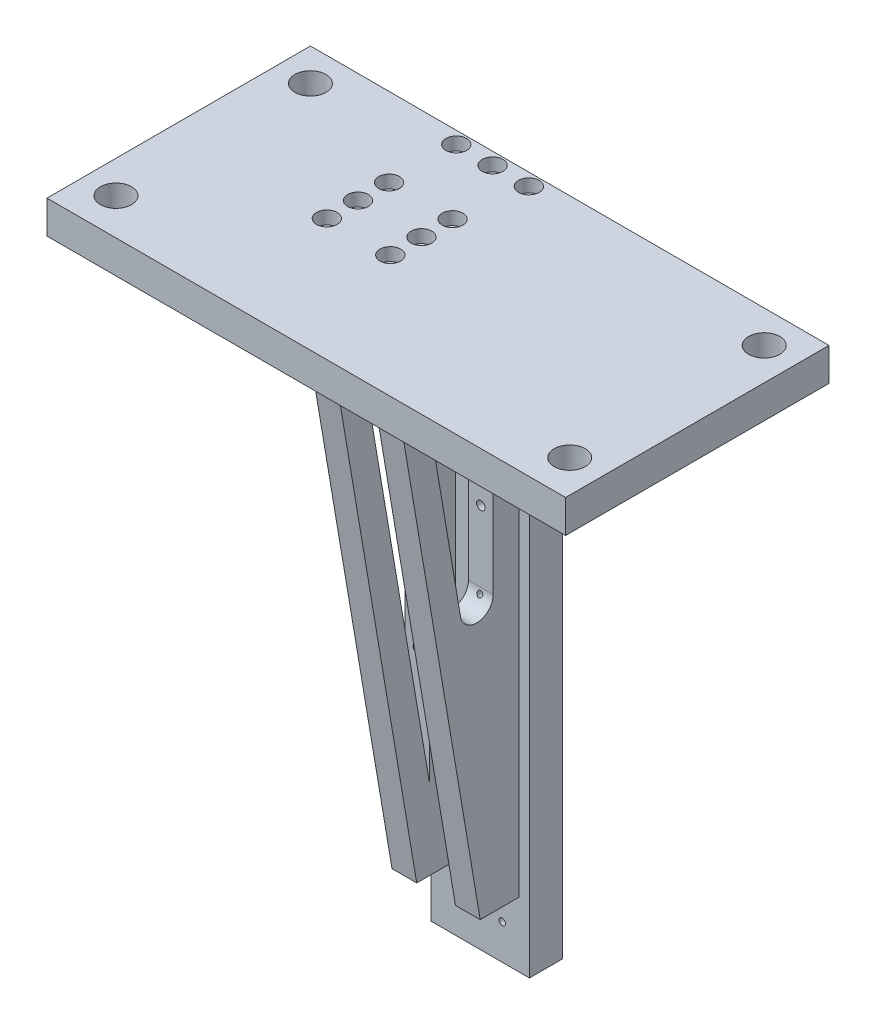
SolidWorks part; units mm, degrees
other "IGNORE"
ref_plane "Front Plane" through (0, 0, 0) normal (0, 0, 1) x (1, 0, 0)
ref_plane "Top Plane" through (0, 0, 0) normal (0, 1, 0) x (1, 0, 0)
ref_plane "Right Plane" through (0, 0, 0) normal (1, 0, 0) x (0, 0, -1)
sketch "Sketch1" plane through (0, 0, 0) normal (1, 0, 0) x (0, 0, -1)
  line L0 (-92.075, 0) -> (9.525, 0)
  line L2 (0, 0) -> (9.525, 0)
  line L4 (9.525, 9.525) -> (-92.075, 9.525)
  line L5 (-92.075, 9.525) -> (-92.075, 0)
  line L7 (0, 0) -> (9.525, 0)
  line L8 (0, 0) -> (0, -250)
  line L9 (0, -250) -> (9.525, -250)
  line L10 (9.525, 0) -> (9.525, -250)
  line L16 (9.525, 9.525) -> (9.525, 0)
  line L17 (-5.005, 0) -> (-5.005, -3.175)
  line L19 (-92.075, 0) -> (-92.075, -3.175)
  line L20 (-92.075, -3.175) -> (9.525, -3.175)
  dimension "D1" = 9.525
  dimension "D2" = 9.525
  dimension "D3" = 101.6
  dimension "D5" = 250
  dimension "D7" = 12.7
  dimension "14.53" = 14.53
extrude "Boss-Extrude5" add sketch "Sketch1" along normal blind 125 and the other way blind 75 contours L16 L4 L5 L0 | L19 L20 L17 L0 region at (0, 4.7625, 41.275) region at (0, -1.5875, 48.54)
extrude "Boss-Extrude6" add sketch "Sketch1<5>" along normal mid plane 38 separate body contours L10 L0 L8 L9 | L8 L20 L10 L0 region at (0, -1.5875, -4.7625) region at (0, -126.5875, -4.7625)
sketch "Sketch1<5>" plane through (0, 0, 0) normal (1, 0, 0) x (0, 0, -1) same geometry as "Sketch1"
sketch "Sketch2" plane through (0, 0, -9.525) normal (0, 0, -1) x (-1, 0, 0)
  line L0 (0, 0) -> (0, -263.8174) construction
  line L1 (-19, 0) -> (-15, 0)
  line L2 (-15, -4.5282) -> (15, -4.5282)
  line L3 (-15, -4.5282) -> (-15, -36.0894)
  line L4 (-15, -36.0894) -> (15, -36.0894)
  line L5 (15, -4.5282) -> (15, -36.0894)
  line L6 (-19, 0) -> (19, 0) construction
  line L7 (-15, 0) -> (-15, -250)
  line L8 (-19, -250) -> (19, -250) construction
  line L9 (-15, -250) -> (-19, -250)
  line L10 (-19, -250) -> (-19, 0)
  line M8 (19, 0) -> (-19, 0)
  line M9 (-19, 0) -> (-19, -250)
  line M10 (-19, -250) -> (19, -250)
  dimension "D1" = 30
  dimension "D2" = 4
extrude "Boss-Extrude7" add sketch "Sketch2" along normal blind 3.175 contours L7 L3 M8 M9 M10 region at (17, -125, -9.525)
sketch "Sketch6" plane through (0, 0, 0) normal (0, -1, 0) x (1, 0, 0)
  line L0 (19, 0) -> (-19, 0) construction
  line L1 (-10, 5.005) -> (10, 5.005)
  line L2 (-10, 5.005) -> (-10, 0)
  line L3 (-10, 0) -> (10, 0)
  line L4 (10, 5.005) -> (10, 0)
  line L5 (0, 0) -> (0, 18.4937) construction
  line L6 (0, -9.525) -> (0, 92.075) construction
  line L7 (19, 0) -> (19, -12.7) construction
  line L8 (19, -2.525) -> (24, -2.525)
  line L9 (19, -2.525) -> (19, -7.525)
  line L10 (19, -7.525) -> (24, -7.525)
  line L11 (24, -2.525) -> (24, -7.525)
  line L12 (-75, -9.525) -> (125, -9.525) construction
  line L13 (-75, 5.005) -> (125, 5.005) construction
  dimension "D2" = 20
  dimension "D3" = 2
  dimension "D4" = 5
  dimension "D5" = 5
extrude "Boss-Extrude8" add sketch "Sketch6" along normal up to vertex (3.175 mm away) up to point (0, -3.175, 92.075)
sketch "Sketch3" plane through (0, 0, 0) normal (0, 1, 0) x (1, 0, 0)
  line L0 (0, 0) -> (0, 9.525) construction
  line L1 (-19, 4.7625) -> (19, 4.7625) construction
  line L2 (-19, 0) -> (-19, 9.525) construction
  line L3 (19, 0) -> (19, 12.7) construction
  line L4 (0, 8.8001) -> (0, 1.2807) construction
  circle A0 centre (-14, 4.7625) radius 2
  circle A1 centre (0, 4.7625) radius 2
  circle A2 centre (14, 4.7625) radius 2
  dimension "D1" = 4
  dimension "D2" = 14
sketch "Sketch7" plane through (0, 0, -9.525) normal (0, 0, -1) x (-1, 0, 0)
  line L0 (-15, 0) -> (-15, -250) construction
  line L1 (-15, -10.1116) -> (-5.475, -10.1116)
  line L2 (-15, -10.1116) -> (-15, -28.0084)
  line L3 (-15, -28.0084) -> (-5.475, -28.0084)
  line L4 (-5.475, -10.1116) -> (-5.475, -28.0084)
  line L5 (9.475, -9.6486) -> (19, -9.6486)
  line L6 (9.475, -9.6486) -> (9.475, -28.9758)
  line L7 (9.475, -28.9758) -> (19, -28.9758)
  line L8 (19, -9.6486) -> (19, -28.9758)
  line L9 (19, 0) -> (19, -250) construction
  dimension "D1" = 9.525
sketch "Sketch5" plane through (0, 0, 0) normal (1, 0, 0) x (0, 0, -1)
  line L0 (-50.8, -3.175) -> (-50.8, -13.175)
  line L1 (-25, -3.175) -> (-25, -11.825)
  line L2 (-50.8, -13.175) -> (-15, -225)
  line L3 (-15, -225) -> (0, -225)
  line L4 (0, 0) -> (0, -250) construction
  line L5 (0, -225) -> (0, -3.175)
  line L6 (0, -3.175) -> (-50.8, -3.175)
  line L7 (0, -250) -> (9.525, -250) construction
  line L9 (-15, -3.175) -> (-15, -11.825)
  line L10 (-8.65, -18.175) -> (0, -18.175)
  line L11 (-8.65, -28.175) -> (0, -28.175)
  line L12 (-40.6582, -13.175) -> (-10, -194.5764)
  line L13 (-10, -194.5764) -> (-10, -194.5764)
  line L14 (-10, -194.5764) -> (-10, -28.1192)
  line L16 (-40.6582, -13.175) -> (-40.6582, -13.175)
  line L17 (-24.9442, -13.175) -> (-40.6582, -13.175)
  line L18 (-10, -13.175) -> (-40.6582, -13.175) construction
  line L19 (-10, -194.5764) -> (-10, -13.175) construction
  line L20 (-92.075, -3.175) -> (-5.005, -3.175) construction
  arc A0 (-15, -11.825) -> (-8.65, -18.175) centre (-8.65, -11.825) ccw
  arc A1 (-25, -11.825) -> (-8.65, -28.175) centre (-8.65, -11.825) ccw
  point P18 (-15, -18.175)
  dimension "D8" = 6.35
  dimension "D1" = 50.8
  dimension "D2" = 15
  dimension "D3" = 25
  dimension "D4" = 10
  dimension "D5" = 221.825
  dimension "D6" = 15
  dimension "D7" = 15
  dimension "D9" = 10
  dimension "D10" = 10
extrude "Boss-Extrude9" add sketch "Sketch5" along normal up to vertex (15 mm away) from vertex separate body contours L10 L9 L6 L0 L2 L3 L5 | L1 A1 L11 L5 L10 A0 L9 L6 region at (0, -5.4507, 37.9) region at (0, -17.4592, 14.2842) up to point (15, -28.0084, -9.525) starting at point (5.475, -28.0084, -9.525)
extrude "Boss-Extrude10" add sketch "Sketch5<3>" against normal up to vertex (19 mm away) from vertex separate body contours L10 L9 L6 L0 L2 L3 L5 | L1 A1 L11 L5 L10 A0 L9 L6 region at (0, -5.4507, 37.9) region at (0, -17.4592, 14.2842) up to point (-19, -9.6486, -9.525) starting at point (-9.475, -9.6486, -9.525)
sketch "Sketch5<3>" plane through (0, 0, 0) normal (1, 0, 0) x (0, 0, -1) same geometry as "Sketch5"
fillet "Fillet1" radius 6.35 4 edges at (10.2375, -194.5764, 10) (10.2375, -28.1192, 10) (10.2375, -13.175, 24.9442) (10.2375, -13.175, 40.6582)
ref_plane "Plane1" through (-2, 0, 0) normal (1, 0, 0) x (0, 0, -1)
sketch "Sketch9" plane through (0, 0, 0) normal (0, 0, -1) x (-1, 0, 0)
  line L0 (-10.2375, -18.175) -> (-10.2375, -225) construction
  line L1 (-15, -18.175) -> (-5.475, -18.175) construction
  line L2 (-15, -225) -> (-5.475, -225) construction
  line L3 (-10.2375, -121.5875) -> (-10.2375, -91.5875) construction
  line L4 (2, -22.6495) -> (2, -218.2945) construction
  line L5 (2, 27.94) -> (2, -27.94) construction
  circle A0 centre (-10.2375, -121.5875) radius 3
  circle A1 centre (-10.2375, -151.5875) radius 3
  circle A2 centre (-10.2375, -181.5875) radius 3
  circle A3 centre (-10.2375, -211.5875) radius 3
  circle A16 centre (-10.2375, -91.5875) radius 3
  circle A17 centre (-10.2375, -61.5875) radius 3
  circle A18 centre (-10.2375, -31.5875) radius 3
  circle A19 centre (14.2375, -211.5875) radius 3
  circle A20 centre (14.2375, -181.5875) radius 3
  circle A21 centre (14.2375, -151.5875) radius 3
  circle A22 centre (14.2375, -121.5875) radius 3
  circle A23 centre (14.2375, -91.5875) radius 3
  circle A24 centre (14.2375, -61.5875) radius 3
  circle A25 centre (14.2375, -31.5875) radius 3
  dimension "D1" = 6
  dimension "D4" = 30
  dimension "D5" = 4
  dimension "D6" = 30
  dimension "D2" = 4
  dimension "D3" = 1
sketch "Sketch8" plane through (0, -3.175, 0) normal (0, 1, 0) x (1, 0, 0)
  line L0 (10.2375, -15) -> (10.2375, -50.8) construction
  line L1 (15, -15) -> (5.475, -15) construction
  line L2 (15, -50.8) -> (5.475, -50.8) construction
  line L3 (5.475, -32.9) -> (15, -32.9) construction
  line L4 (5.475, -15) -> (5.475, -50.8) construction
  line L5 (15, -15) -> (15, -50.8) construction
  line L7 (-2, 31.7466) -> (-2, -84.8925) construction
  line L8 (-2, -27.94) -> (-2, 27.94) construction
  circle A0 centre (10.2375, -20.9) radius 3
  circle A1 centre (10.2375, -32.9) radius 3
  circle A2 centre (10.2375, -44.9) radius 3
  circle A3 centre (-14.2375, -44.9) radius 3
  circle A4 centre (-14.2375, -32.9) radius 3
  circle A5 centre (-14.2375, -20.9) radius 3
  dimension "D2" = 6
  dimension "D1" = 12
hole_wizard "CBORE for M4 SHCS1" positions "Sketch12" profile "Sketch13" counterbore size "M4" standard "ANSI Metric" end condition through all
sketch "Sketch12" plane through (0, 0, -9.525) normal (0, 0, -1) x (-1, 0, 0)
  line L0 (-10.2375, -18.175) -> (-10.2375, -225) construction
  point P0 (-10.2375, -61.5875)
  point P3 (-10.2375, -31.5875)
  point P6 (-10.2375, -91.5875)
  point P9 (-10.2375, -121.5875)
  point P13 (-10.2375, -151.5875)
  point P16 (-10.2375, -181.5875)
  point P19 (-10.2375, -211.5875)
  point P22 (14.2375, -211.5875)
  point P25 (14.2375, -181.5875)
  point P28 (14.2375, -151.5875)
  point P31 (14.2375, -121.5875)
  point P34 (14.2375, -91.5875)
  point P37 (14.2375, -61.5875)
  point P40 (14.2375, -31.5875)
sketch "Sketch13" plane through (10.2375, -61.5875, -9.525) normal (1, 0, 0) x (0, 1, 0)
  line L0 (0, 0) -> (0, 101.6)
  line L1 (0, 101.6) -> (2.4, 101.6)
  line L3 (2.4, 101.6) -> (2.4, 5)
  line L4 (2.4, 5) -> (4, 5)
  line L5 (4, 5) -> (4, 0)
  line L7 (4, 0) -> (0, 0)
  line L11 (0, -6.35) -> (0, 107.95) construction
  dimension "Thru Hole Dia." = 4.8
  dimension "Thru Hole Depth" = 101.6
  dimension "C'Bore Dia." = 8
  dimension "C'Bore Depth" = 5
hole_wizard "CBORE for M4 SHCS2" positions "Sketch14" profile "Sketch15" counterbore size "M4" standard "ANSI Metric" end condition through all
sketch "Sketch14" plane through (0, 9.525, 0) normal (0, 1, 0) x (1, 0, 0)
  line L0 (-19, 4.7625) -> (19, 4.7625) construction
  point P0 (-14.2375, -20.9)
  point P3 (-14.2375, -32.9)
  point P6 (-14.2375, -44.9)
  point P9 (10.2375, -44.9)
  point P12 (10.2375, -32.9)
  point P15 (10.2375, -20.9)
  point P18 (14, 4.7625)
  point P21 (0, 4.7625)
  point P25 (-14, 4.7625)
sketch "Sketch15" plane through (-14.2375, 9.525, 20.9) normal (1, 0, 0) x (0, 0, 1)
  line L0 (0, 0) -> (0, 259.525)
  line L1 (0, 259.525) -> (2.4, 259.525)
  line L3 (2.4, 259.525) -> (2.4, 5)
  line L4 (2.4, 5) -> (4, 5)
  line L5 (4, 5) -> (4, 0)
  line L7 (4, 0) -> (0, 0)
  line L11 (0, -6.35) -> (0, 107.95) construction
  dimension "Thru Hole Dia." = 4.8
  dimension "Thru Hole Depth" = 259.525
  dimension "C'Bore Dia." = 8
  dimension "C'Bore Depth" = 5
hole_wizard "M4x0.7 Tapped Hole1" positions "Sketch16" profile "Sketch17" tap size "M4x0.7" standard "ANSI Metric"
sketch "Sketch16" plane through (0, -3.175, 0) normal (0, 1, 0) x (1, 0, 0)
  point P0 (10.2375, -20.9)
  point P3 (10.2375, -32.9)
  point P6 (10.2375, -44.9)
  point P9 (-14.2375, -44.9)
  point P12 (-14.2375, -32.9)
  point P15 (-14.2375, -20.9)
sketch "Sketch17" plane through (10.2375, -3.175, 20.9) normal (1, 0, 0) x (0, 0, 1)
  line L0 (0, 0) -> (0, 11.0914)
  line L1 (0, 11.0914) -> (1.65, 10.1)
  line L2 (1.65, 10.1) -> (1.65, 0)
  line L5 (1.65, 0) -> (0, 0)
  line L10 (0, 11.0914) -> (-1.65, 10.1) construction
  line L11 (0, -6.35) -> (0, 107.95) construction
  dimension "Tap Drill Dia." = 3.3
  dimension "Tap Drill Depth" = 10.1
  dimension "Drill Angle" = 118
hole_wizard "M4x0.7 Tapped Hole2" positions "Sketch18" profile "Sketch19" tap size "M4x0.7" standard "ANSI Metric"
sketch "Sketch18" plane through (0, 0, 0) normal (0, 0, -1) x (-1, 0, 0)
  line L0 (-10.2375, -18.175) -> (-10.2375, -225) construction
  point P0 (-10.2375, -31.5875)
  point P3 (14.2375, -31.5875)
  point P6 (14.2375, -61.5875)
  point P9 (-10.2375, -61.5875)
  point P12 (-10.2375, -91.5875)
  point P15 (14.2375, -91.5875)
  point P18 (-10.2375, -121.5875)
  point P22 (14.2375, -121.5875)
  point P25 (-10.2375, -151.5875)
  point P28 (14.2375, -151.5875)
  point P31 (-10.2375, -181.5875)
  point P34 (14.2375, -181.5875)
  point P37 (-10.2375, -211.5875)
  point P40 (14.2375, -211.5875)
sketch "Sketch19" plane through (10.2375, -31.5875, 0) normal (1, 0, 0) x (0, 1, 0)
  line L0 (0, 0) -> (0, 11.0914)
  line L1 (0, 11.0914) -> (1.65, 10.1)
  line L2 (1.65, 10.1) -> (1.65, 0)
  line L5 (1.65, 0) -> (0, 0)
  line L10 (0, 11.0914) -> (-1.65, 10.1) construction
  line L11 (0, -6.35) -> (0, 107.95) construction
  dimension "Tap Drill Dia." = 3.3
  dimension "Tap Drill Depth" = 10.1
  dimension "Drill Angle" = 118
sketch "Sketch20" plane through (0, 9.525, 0) normal (0, 1, 0) x (1, 0, 0)
  line L0 (25, 9.525) -> (25, -92.075) construction
  line L1 (-75, 9.525) -> (125, 9.525) construction
  line L2 (-75, -92.075) -> (125, -92.075) construction
  line L3 (-75, 9.525) -> (-75, -92.075) construction
  circle A0 centre (-62.5, -2.975) radius 5
  circle A1 centre (-62.5, -77.975) radius 5
  circle A2 centre (112.5, -77.975) radius 5
  circle A3 centre (112.5, -2.975) radius 5
  dimension "D1" = 10
  dimension "D2" = 12.5
  dimension "D3" = 12.5
  dimension "D4" = 75
sketch "Sketch23" plane through (0, 0, 0) normal (0, -1, 0) x (1, 0, 0)
  line L0 (-75, 5.005) -> (-10, 5.005) construction
  line L1 (10, 5.005) -> (125, 5.005) construction
  line L3 (125, -9.525) -> (45, -9.525)
  line L4 (-40, 5.005) -> (-75, 5.005)
  line L5 (-40, 5.005) -> (-40, -9.525)
  line L6 (-40, -9.525) -> (-75, -9.525)
  line L7 (-75, 5.005) -> (-75, -9.525)
  line L8 (125, -9.525) -> (125, 5.005)
  line L9 (125, 5.005) -> (45, 5.005)
  line L10 (45, -9.525) -> (45, 5.005)
  dimension "D1" = 35
  dimension "50" = 80
fillet "Fillet2" radius 6.35 2 edges at (10, -1.5875, 5.005) (-10, -1.5875, 5.005)
extrude "Boss-Extrude11" add sketch "Sketch23" along normal up to surface (3.175 mm away) up to face at (-14.2375, -3.175, 18.5)
hole_wizard "M10 Clearance Hole1" positions "Sketch21" profile "Sketch22" hole size "M10" standard "ANSI Metric" end condition through all
sketch "Sketch21" plane through (0, 9.525, 0) normal (0, 1, 0) x (1, 0, 0)
  point P0 (-62.5, -2.975)
  point P3 (-62.5, -77.975)
  point P6 (112.5, -77.975)
  point P9 (112.5, -2.975)
sketch "Sketch22" plane through (-62.5, 9.525, 2.975) normal (1, 0, 0) x (0, 0, 1)
  line L0 (0, 0) -> (0, 259.525)
  line L1 (0, 259.525) -> (6, 259.525)
  line L2 (6, 259.525) -> (6, 0)
  line L5 (6, 0) -> (0, 0)
  line L11 (0, -6.35) -> (0, 107.95) construction
  dimension "Thru Hole Dia." = 12
  dimension "Thru Hole Depth" = 259.525
fillet "Fillet3" radius 6.35 2 edges at (45, -1.5875, 5.005) (-40, -1.5875, 5.005)
hole_wizard "M4x0.7 Tapped Hole3" positions "Sketch24" profile "Sketch25" tap size "M4x0.7" standard "ANSI Metric"
sketch "Sketch24" plane through (0, 0, 0) normal (0, 1, 0) x (1, 0, 0)
  point P0 (-14, 4.7625)
  point P3 (0, 4.7625)
  point P6 (14, 4.7625)
sketch "Sketch25" plane through (-14, 0, -4.7625) normal (1, 0, 0) x (0, 0, 1)
  line L0 (0, 0) -> (0, 11.0914)
  line L1 (0, 11.0914) -> (1.65, 10.1)
  line L2 (1.65, 10.1) -> (1.65, 0)
  line L5 (1.65, 0) -> (0, 0)
  line L10 (0, 11.0914) -> (-1.65, 10.1) construction
  line L11 (0, -6.35) -> (0, 107.95) construction
  dimension "Tap Drill Dia." = 3.3
  dimension "Tap Drill Depth" = 10.1
  dimension "Drill Angle" = 118
sketch "Sketch26" plane through (0, 0, -9.525) normal (0, 0, -1) x (-1, 0, 0)
  line L0 (0, -11.1171) -> (0, -57.3944) construction
  line L1 (-15, 0) -> (-15, -250) construction
  line L2 (40, 0) -> (-45, 0) construction
  circle A0 centre (-8.5, -11.475) radius 1.5
  circle A1 centre (8.5, -11.475) radius 1.5
  circle A2 centre (-8.5, -236.475) radius 1.5
  circle A3 centre (8.5, -236.475) radius 1.5
  dimension "D2" = 3
  dimension "D1" = 15
  dimension "D3" = 17
  dimension "D4" = 11.475
  dimension "D5" = 225
hole_wizard "M3x0.5 Tapped Hole1" positions "Sketch27" profile "Sketch28" tap size "M3x0.5" standard "ANSI Metric" end condition through all
sketch "Sketch27" plane through (0, 0, -9.525) normal (0, 0, -1) x (-1, 0, 0)
  point P0 (-8.5, -11.475)
  point P3 (8.5, -11.475)
  point P6 (-8.5, -236.475)
  point P9 (8.5, -236.475)
sketch "Sketch28" plane through (8.5, -11.475, -9.525) normal (1, 0, 0) x (0, 1, 0)
  line L0 (0, 0) -> (0, 101.6)
  line L1 (0, 101.6) -> (1.25, 101.6)
  line L2 (1.25, 101.6) -> (1.25, 0)
  line L5 (1.25, 0) -> (0, 0)
  line L11 (0, -6.35) -> (0, 107.95) construction
  dimension "Thru Tap Drill Dia." = 2.5
  dimension "Thru Tap Drill Depth" = 101.6
cosmetic thread "Hole Thread1" parameters "D2"=3
cosmetic thread "Hole Thread2" parameters "D2"=3
cosmetic thread "Hole Thread3" parameters "D2"=3
cosmetic thread "Hole Thread4" parameters "D2"=3
